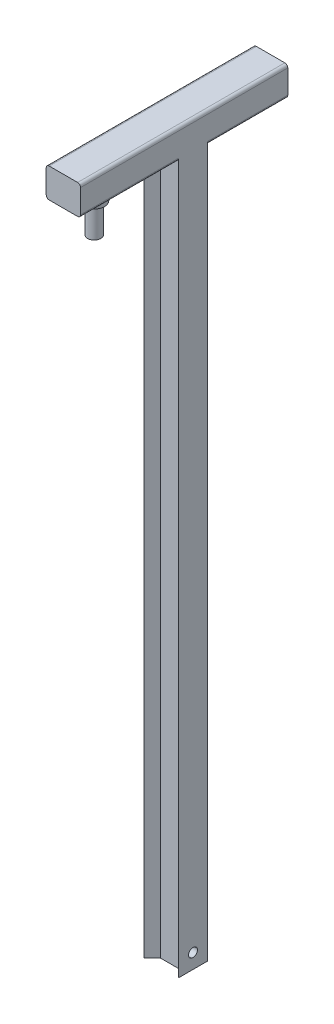
SolidWorks part; units mm, degrees
ref_plane "Front Plane" through (0, 0, 0) normal (0, 0, 1) x (1, 0, 0)
ref_plane "Top Plane" through (0, 0, 0) normal (0, 1, 0) x (1, 0, 0)
ref_plane "Right Plane" through (0, 0, 0) normal (1, 0, 0) x (0, 0, -1)
sketch "Sketch1" plane through (0, 0, 0) normal (0, 1, 0) x (1, 0, 0)
  line L0 (0, 0) -> (-2.8284, -2.8284)
  line L1 (-2.8284, -2.8284) -> (-8.8284, -2.8284)
  line L2 (-8.8284, -2.8284) -> (-11.6569, 0)
  line L3 (-11.6569, 0) -> (-11.6569, -10)
  line L4 (-11.6569, -10) -> (-8.8284, -7.1716)
  line L5 (-8.8284, -7.1716) -> (-2.8284, -7.1716)
  line L6 (-2.8284, -7.1716) -> (0, -10)
  line L7 (0, -10) -> (0, 0)
  dimension "D1" = 6
  dimension "D2" = 6
  dimension "D3" = 135
  dimension "D4" = 135
  dimension "D5" = 10
  dimension "D6" = 10
  dimension "D7" = 4
  dimension "D8" = 4
extrude "Boss-Extrude1" add sketch "Sketch1" along normal blind 240
sketch "Sketch2" plane through (0, 0, 0) normal (0, -1, 0) x (1, 0, 0)
  line L1 (0, 0) -> (-11.6569, 0)
  line L2 (0, 0) -> (0, 10)
  line L3 (0, 10) -> (-11.6569, 10)
  line L4 (-11.6569, 0) -> (-11.6569, 10)
extrude "Boss-Extrude2" add sketch "Sketch2" along normal blind 10
sketch "Sketch3" plane through (-11.6569, 0, 0) normal (-1, 0, 0) x (0, 0, 1)
  line L0 (10, -10) -> (0, -10) construction
  line L2 (0, -10) -> (0, 0) construction
  circle A0 centre (5, -5) radius 1.5
  point P4 (5, -10)
  point P7 (0, -5)
  dimension "D1" = 0
  dimension "D2" = 0
  dimension "D3" = 3
extrude "Cut-Extrude1" cut sketch "Sketch3" against normal blind 30
sketch "Sketch4" plane through (0, 0, 2.8284) normal (0, 0, -1) x (-1, 0, 0)
  line L0 (0, 240) -> (0, 0) construction
  line L1 (0, 240) -> (11.6569, 240)
  line L2 (0, 240) -> (0, 230)
  line L3 (0, 230) -> (11.6569, 230)
  line L4 (11.6569, 240) -> (11.6569, 230)
  line L5 (11.6569, 240) -> (11.6569, 0) construction
  line L6 (2.8284, 240) -> (8.8284, 240) construction
  dimension "D1" = 0
  dimension "D2" = 0
  dimension "D3" = 0
  dimension "D4" = 10
extrude "Boss-Extrude3" add sketch "Sketch4" along normal blind 30
sketch "Sketch5" plane through (0, 0, 7.1716) normal (0, 0, 1) x (1, 0, 0)
  line L0 (0, 240) -> (0, 0) construction
  line L1 (0, 240) -> (-11.6569, 240)
  line L2 (0, 240) -> (0, 230)
  line L3 (0, 230) -> (-11.6569, 230)
  line L4 (-11.6569, 240) -> (-11.6569, 230)
  line L5 (-8.8284, 240) -> (-2.8284, 240) construction
  dimension "D1" = 0
  dimension "D2" = 0
  dimension "D3" = 0
  dimension "D4" = 10
extrude "Boss-Extrude4" add sketch "Sketch5" along normal blind 36
sketch "Sketch7" plane through (0, 230, 0) normal (0, -1, 0) x (1, 0, 0)
  line L0 (-11.6569, 43.1716) -> (0, 43.1716) construction
  circle A0 centre (-5.8284, 32.7116) radius 2.25
  point P4 (-5.8284, 43.1716)
  dimension "D1" = 10.46
  dimension "D2" = 4.5
  dimension "D3" = 0
extrude "Boss-Extrude6" add sketch "Sketch7" along normal blind 13
sketch "Sketch8" plane through (0, 0, -27.1716) normal (0, 0, -1) x (-1, 0, 0)
  line L0 (0, 230) -> (11.6569, 230) construction
  line L1 (11.6569, 230) -> (11.6569, 240) construction
  circle A0 centre (5.8284, 235) radius 2.75
  point P4 (5.8284, 230)
  point P7 (11.6569, 235)
  dimension "D1" = 0
  dimension "D2" = 0
  dimension "D3" = 5.5
extrude "Cut-Extrude2" cut sketch "Sketch8" against normal blind 10
sketch "Sketch9" plane through (0, 230, 0) normal (0, -1, 0) x (-1, 0, 0)
  circle A1 centre (5.8284, -32.7116) radius 3.5
  dimension "D1" = 7
extrude "Boss-Extrude7" add sketch "Sketch9" along normal blind 3
thread "Thread1" pitch 2.1167 method cut profile "Thread Profile1" start angle 0, offset 0, length 8, pitch 2.1167, diameter 5.5
ref_plane "Plane1" through (-3.0784, 235, -27.1716) normal (0, -1, 0) x (1, 0, 0)
sketch "Thread Profile1" plane through (-3.0784, 235, -27.1716) normal (0, -1, 0) x (1, 0, 0)
  line L0 (0, 0) -> (0, 2.1167) construction
  line L1 (0, 0) -> (1.1457, 0.6615)
  line L2 (1.1457, 0.6615) -> (1.1457, 0.926)
  line L3 (1.1457, 0.926) -> (0, 1.5875)
  line L4 (1.1457, 0.7937) -> (0, 0.7937) construction
  line L11 (0, 0) -> (0, 1.5875)
  point P2 (0, 0)
  dimension "Pitch" = 2.1167
  dimension "Profile_Angle" = 60
  dimension "Profile_Land" = 0.2646
  dimension "Profile_Height" = 1.1457
sketch "Sketch12" plane through (0, 0, -27.1716) normal (0, 0, -1) x (-1, 0, 0)
  circle A0 centre (5.8284, 235) radius 3.75
  dimension "D1" = 7.5
extrude "Cut-Extrude3" cut sketch "Sketch12" against normal blind 2
fillet "Fillet1" radius 1 6 edges at (0, 240, 8) (0, 230, -13.5858) (-11.6569, 230, -13.5858) (-11.6569, 240, 8) (0, 230, 26.5858) (-11.6569, 230, 26.5858)
sketch "Sketch13" plane through (0, 0, 0) normal (0, 1, 0) x (1, 0, 0)
  line L0 (-11.6569, 0) -> (-8.8284, -2.8284)
  line L1 (-8.8284, -2.8284) -> (-2.8284, -2.8284)
  line L2 (-2.8284, -2.8284) -> (0, 0)
  line L3 (0, 0) -> (-11.6569, 0)
  line L4 (-8.8284, -7.1716) -> (-2.8284, -7.1716)
  line L5 (-2.8284, -7.1716) -> (0, -10)
  line L6 (0, -10) -> (-11.6569, -10)
  line L7 (-11.6569, -10) -> (-8.8284, -7.1716)
extrude "Cut-Extrude4" cut sketch "Sketch13" against normal blind 20
